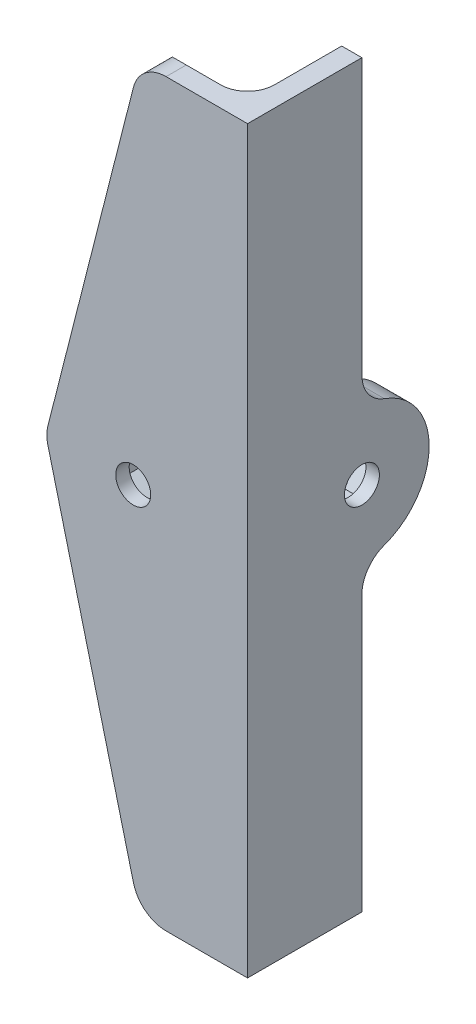
SolidWorks part; units mm, degrees
ref_plane "Front Plane" through (0, 0, 0) normal (0, 0, 1) x (1, 0, 0)
ref_plane "Top Plane" through (0, 0, 0) normal (0, 1, 0) x (1, 0, 0)
ref_plane "Right Plane" through (0, 0, 0) normal (1, 0, 0) x (0, 0, -1)
sketch "Sketch1" plane through (0, 0, 0) normal (0, 1, 0) x (1, 0, 0)
  line L0 (0, 0) -> (30, 0)
  line L1 (30, 0) -> (30, 30)
  line L2 (30, 30) -> (25, 30)
  line L3 (25, 30) -> (25, 5)
  line L4 (25, 5) -> (0, 5)
  line L5 (0, 5) -> (0, 0)
  dimension "D1" = 30
  dimension "D2" = 30
  dimension "D3" = 5
  dimension "D4" = 5
extrude "Boss-Extrude1" add sketch "Sketch1" along normal blind 30
sketch "Sketch2" plane through (0, 0, 0) normal (0, 0, 1) x (1, 0, 0)
  circle A0 centre (13, 15) radius 2.6
extrude "Cut-Extrude1" cut sketch "Sketch2" against normal through all both
sketch "Sketch3" plane through (30, 0, 0) normal (1, 0, 0) x (0, 0, -1)
  circle A0 centre (17, 15) radius 2.6
extrude "Cut-Extrude2" cut sketch "Sketch3" against normal through all both
sketch "Sketch4" plane through (25, 0, 0) normal (-1, 0, 0) x (0, 0, 1)
  line L1 (-21.9075, 15) -> (-19.4537, 10.75)
  line L2 (-19.4537, 10.75) -> (-14.5463, 10.75)
  line L3 (-14.5463, 10.75) -> (-12.0925, 15)
  line L4 (-12.0925, 15) -> (-14.5463, 19.25)
  line L5 (-14.5463, 19.25) -> (-19.4537, 19.25)
  line L6 (-19.4537, 19.25) -> (-21.9075, 15)
  circle A0 centre (-17, 15) radius 4.25 construction
  dimension "D1" = 8.5
extrude "Cut-Extrude3" cut sketch "Sketch4" against normal offset from surface (3 mm away) 2 up to face at (30, 15, -19.6)
sketch "Sketch5" plane through (0, 0, -5) normal (0, 0, -1) x (-1, 0, 0)
  line L1 (-17.1, 17.3671) -> (-17.1, 12.6329)
  line L2 (-17.1, 12.6329) -> (-13, 10.2657)
  line L3 (-13, 10.2657) -> (-8.9, 12.6329)
  line L4 (-8.9, 12.6329) -> (-8.9, 17.3671)
  line L5 (-8.9, 17.3671) -> (-13, 19.7343)
  line L6 (-13, 19.7343) -> (-17.1, 17.3671)
  circle A0 centre (-13, 15) radius 4.1 construction
  dimension "D1" = 8.2
extrude "Cut-Extrude4" cut sketch "Sketch5" against normal offset from surface (3 mm away) 2 up to face at (15.6, 15, 0)
sketch "Sketch8" plane through (0, 30, 0) normal (0, 1, 0) x (1, 0, 0)
  line L0 (0, 5) -> (25, 5)
  line L1 (25, 5) -> (25, 30)
  line L2 (25, 30) -> (30, 30)
  line L3 (30, 30) -> (30, 0)
  line L4 (30, 0) -> (0, 0)
  line L5 (0, 0) -> (0, 5)
extrude "Boss-Extrude4" add sketch "Sketch8" along normal blind 40
extrude "Boss-Extrude5" add sketch "Sketch8<2>" against normal blind 40 from surface starting at face at (18.3333, 0, -11.6667)
sketch "Sketch8<2>" plane through (0, 30, 0) normal (0, 1, 0) x (1, 0, 0) same geometry as "Sketch8"
fillet "Fillet2" radius 5 4 edges at (27.5, 70, -30) (0, 70, -2.5) (0, -40, -2.5) (27.5, -40, -30)
fillet "Fillet3" radius 2 1 edges at (25, 15, -5)
chamfer "Chamfer2" distance 2 angle 45 12 edges at (14, 70, -5) (24.4142, 70, -5.5858) (1.4645, 68.5355, -5) (25, 70, -16) (0, 15, -5) (25, 68.5355, -28.5355) (1.4645, -38.5355, -5) (25, 15, -30) (14, -40, -5) (25, -38.5355, -28.5355) (24.4142, -40, -5.5858) (25, -40, -16)
sketch "Sketch11" plane through (25, 0, 0) normal (-1, 0, 0) x (0, 0, 1)
  line L0 (-17, 25) -> (-17, 79.1765)
  line L2 (-17, 79.1765) -> (-82.4909, 30.9166)
  line L3 (-82.4909, 30.9166) -> (-67.4974, -40.745)
  line L4 (-67.4974, -40.745) -> (-17, -61.1146)
  line L5 (-17, -61.1146) -> (-17, 5)
  arc A0 (-17, 25) -> (-17, 5) centre (-17, 15) ccw
extrude "Cut-Extrude7" cut sketch "Sketch11" against normal through all both
fillet "Fillet4" radius 5 2 edges at (27.5, 25, -17) (27.5, 5, -17)
sketch "Sketch12" plane through (0, 0, -5) normal (0, 0, -1) x (-1, 0, 0)
  line L0 (-14, 70) -> (0, 15)
  line L1 (-23, 70) -> (-5, 70) construction
  line L2 (0, 65) -> (0, -35) construction
  line L3 (0, 15) -> (-14, -40)
  line L4 (-5, -40) -> (-23, -40) construction
  line L5 (-14, -40) -> (29.605, -51.0995)
  line L6 (29.605, -51.0995) -> (59.9547, 7.9504)
  line L7 (59.9547, 7.9504) -> (29.605, 77.9866)
  line L8 (29.605, 77.9866) -> (-23, 76.936)
  line L9 (-23, 76.936) -> (-14, 70)
extrude "Cut-Extrude8" cut sketch "Sketch12" against normal through all both
fillet "Fillet5" radius 5 3 edges at (14, -40, -1.5) (14, 70, -1.5) (0, 15, -1.5)
